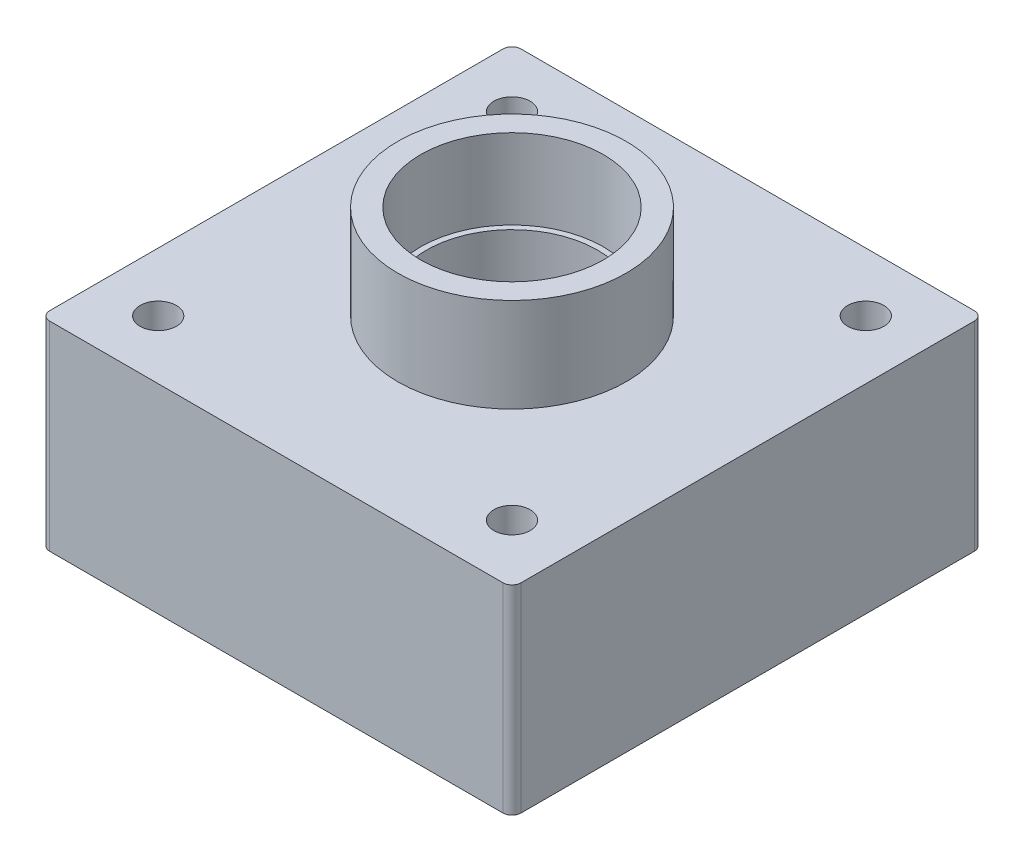
SolidWorks part; units mm, degrees
ref_plane "Front Plane" through (0, 0, 0) normal (0, 0, 1) x (1, 0, 0)
ref_plane "Top Plane" through (0, 0, 0) normal (0, 1, 0) x (1, 0, 0)
ref_plane "Right Plane" through (0, 0, 0) normal (1, 0, 0) x (0, 0, -1)
sketch "Sketch1" plane through (0, 0, 0) normal (0, 1, 0) x (1, 0, 0)
  line L1 (-79.375, -82.55) -> (79.375, -82.55)
  line L2 (-82.55, -79.375) -> (-82.55, 79.375)
  line L3 (-79.375, 82.55) -> (79.375, 82.55)
  line L4 (82.55, -79.375) -> (82.55, 79.375)
  line L5 (-82.55, -82.55) -> (82.55, 82.55) construction
  line L6 (-82.55, 82.55) -> (82.55, -82.55) construction
  circle A0 centre (0, 0) radius 87.63 construction
  circle A1 centre (61.9638, 61.9638) radius 6.35
  circle A2 centre (61.9638, -61.9638) radius 6.35
  circle A3 centre (-61.9638, -61.9638) radius 6.35
  circle A4 centre (-61.9638, 61.9638) radius 6.35
  circle A5 centre (0, 0) radius 69.85
  circle A6 centre (0, 0) radius 76.2
  circle A7 centre (0, 0) radius 20
  arc A8 (79.375, -82.55) -> (82.55, -79.375) centre (79.375, -79.375) ccw
  arc A9 (-79.375, -82.55) -> (-82.55, -79.375) centre (-79.375, -79.375) cw
  arc A10 (-82.55, 79.375) -> (-79.375, 82.55) centre (-79.375, 79.375) cw
  arc A11 (79.375, 82.55) -> (82.55, 79.375) centre (79.375, 79.375) cw
  point P0 (0, 0)
  point P19 (0, 0)
  dimension "D2" = 175.26
  dimension "D3" = 12.7
  dimension "D5" = 139.7
  dimension "D6" = 152.4
  dimension "D7" = 40
  dimension "D8" = 3.175
  dimension "D1" = 165.1
  dimension "D4" = 4
extrude "Boss-Extrude1" add sketch "Sketch1" along normal blind 69.85 contours A11 L3 A10 L2 A9 L1 A8 L4 A6 A4 A3 A2 A1 | A6 A5 | A5 A7 | A7 region at (-79.9691, 0, 79.9691) region at (-67.8743, 0, 0) region at (-74.0447, 0, 0) region at (0, 0, 0)
extrude "Cut-Extrude1" cut sketch "Sketch1<3>" along normal blind 40 contours A7 region at (0, 0, 0)
sketch "Sketch1<3>" plane through (0, 0, 0) normal (0, 1, 0) x (1, 0, 0) same geometry as "Sketch1"
extrude "Cut-Extrude2" cut sketch "Sketch1<4>" along normal blind 8 contours A6 A5 region at (-74.0447, 0, 0)
sketch "Sketch1<4>" plane through (0, 0, 0) normal (0, 1, 0) x (1, 0, 0) same geometry as "Sketch1"
sketch "Sketch2" plane through (0, 69.85, 0) normal (0, 1, 0) x (1, 0, 0)
  circle A0 centre (0, 0) radius 40
  circle A1 centre (0, 0) radius 27
  circle A2 centre (0, 0) radius 30
  dimension "D1" = 80
  dimension "D2" = 54
  dimension "D3" = 60
extrude "Boss-Extrude2" add sketch "Sketch2" along normal blind 32.95 contours A0 A2 | A2 A1 | A1 region at (-38.8686, 69.85, 0) region at (0, 69.85, 0) region at (-29.1515, 69.85, 0)
sketch "Sketch3" plane through (0, 102.8, 0) normal (0, 1, 0) x (1, 0, 0)
  circle A0 centre (0, 0) radius 32
  dimension "D1" = 64
extrude "Cut-Extrude5" cut sketch "Sketch3" against normal blind 28
sketch "Sketch4" plane through (0, 74.8, 0) normal (0, 1, 0) x (1, 0, 0)
  circle A0 centre (0, 0) radius 30
  dimension "D1" = 60
extrude "Cut-Extrude6" cut sketch "Sketch4" against normal blind 22
sketch "Sketch11" plane through (-82.55, 0, 0) normal (-1, 0, 0) x (0, 0, 1)
  point P0 (0, 25.4)
  dimension "D1" = 25.4
hole_wizard "1/2-14 NPSM Tapped Hole2" positions "Sketch11" profile "Sketch10" tap size "1/2-14 NPSM" standard "ANSI Inch"
sketch "Sketch10" plane through (-82.55, 25.4, 0) normal (0, 1, 0) x (0, 0, 1)
  line L0 (0, 0) -> (0, 41.91)
  line L1 (0, 41.91) -> (9.4869, 41.91)
  line L2 (9.4869, 41.91) -> (9.4869, 0)
  line L5 (9.4869, 0) -> (0, 0)
  line L10 (0, 41.91) -> (-9.4869, 41.91) construction
  line L11 (0, -6.35) -> (0, 107.95) construction
  dimension "Tap Drill Dia." = 18.9738
  dimension "Tap Drill Depth" = 41.91
  dimension "Drill Angle" = 180
cosmetic thread "Hole Thread2" parameters "D1"=41.81, "D2"=20.9042
sketch "Sketch12" plane through (0, 0, 0) normal (0, -1, 0) x (1, 0, 0)
  line L0 (-82.55, 79.375) -> (-82.55, -79.375) construction
  circle A0 centre (-50.55, 0) radius 6.35
  point P2 (0, 0)
  dimension "D1" = 12.7
  dimension "D2" = 32
extrude "Cut-Extrude7" cut sketch "Sketch12" against normal up to next
